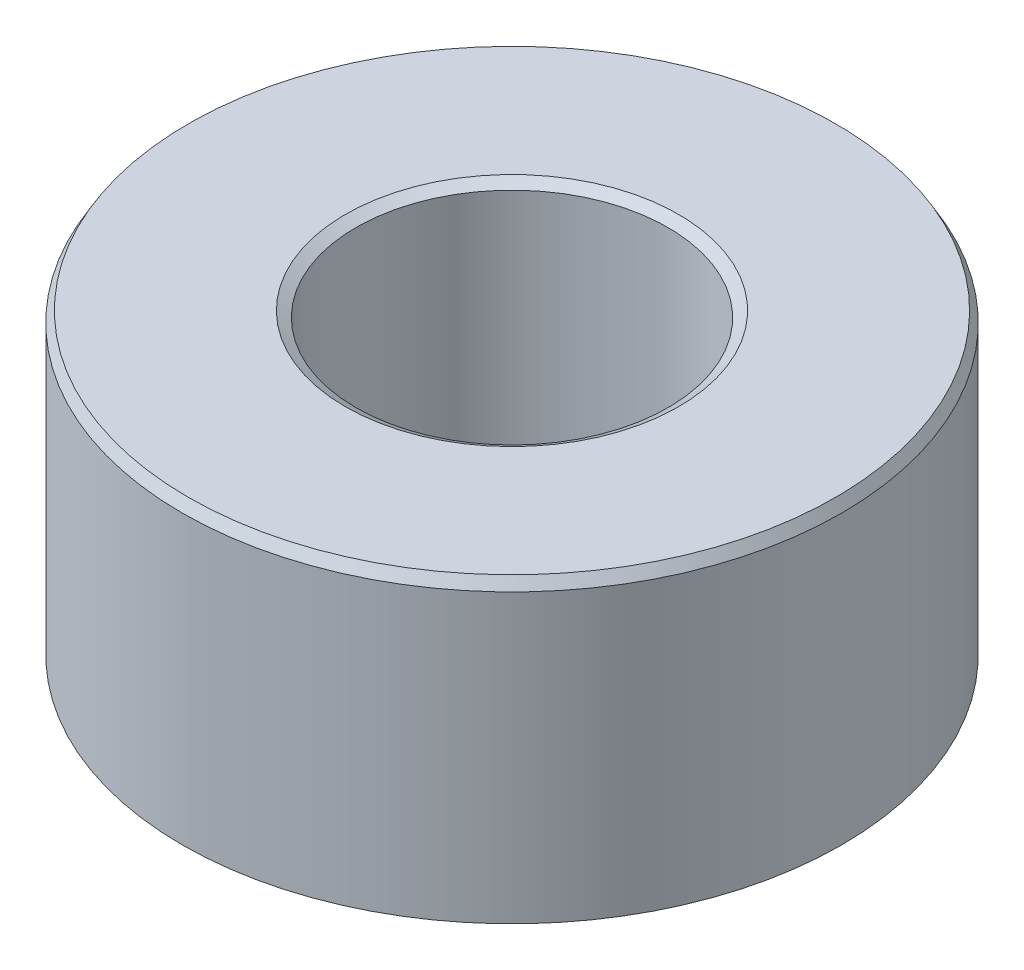
SolidWorks part; units mm, degrees
ref_plane "Front Plane" through (0, 0, 0) normal (0, 0, 1) x (1, 0, 0)
ref_plane "Top Plane" through (0, 0, 0) normal (0, 1, 0) x (1, 0, 0)
ref_plane "Right Plane" through (0, 0, 0) normal (1, 0, 0) x (0, 0, -1)
sketch "Sketch1" plane through (0, 0, 0) normal (0, 1, 0) x (1, 0, 0)
  circle A0 centre (0, 0) radius 7.5
  dimension "SLEEVE_OD" = 15
extrude "Boss-Extrude1" add sketch "Sketch1" along normal blind 6.917
sketch "Sketch2" plane through (0, 0, 0) normal (0, 1, 0) x (1, 0, 0)
  circle A0 centre (0, 0) radius 3.55
  dimension "BORE_D" = 7.0999
extrude "Cut-Extrude1" cut sketch "Sketch2" along normal through all
chamfer "Chamfer1" distance 0.2404 angle 30 4 edges at (0, 6.917, 3.55) (0, 0, 3.55) (0, 0, 7.5) (0, 6.917, 7.5) first distance on face at (0, 6.917, 3.55) first distance on face at (0, 0, 3.55) first distance on face at (0, 6.917, 7.5)
